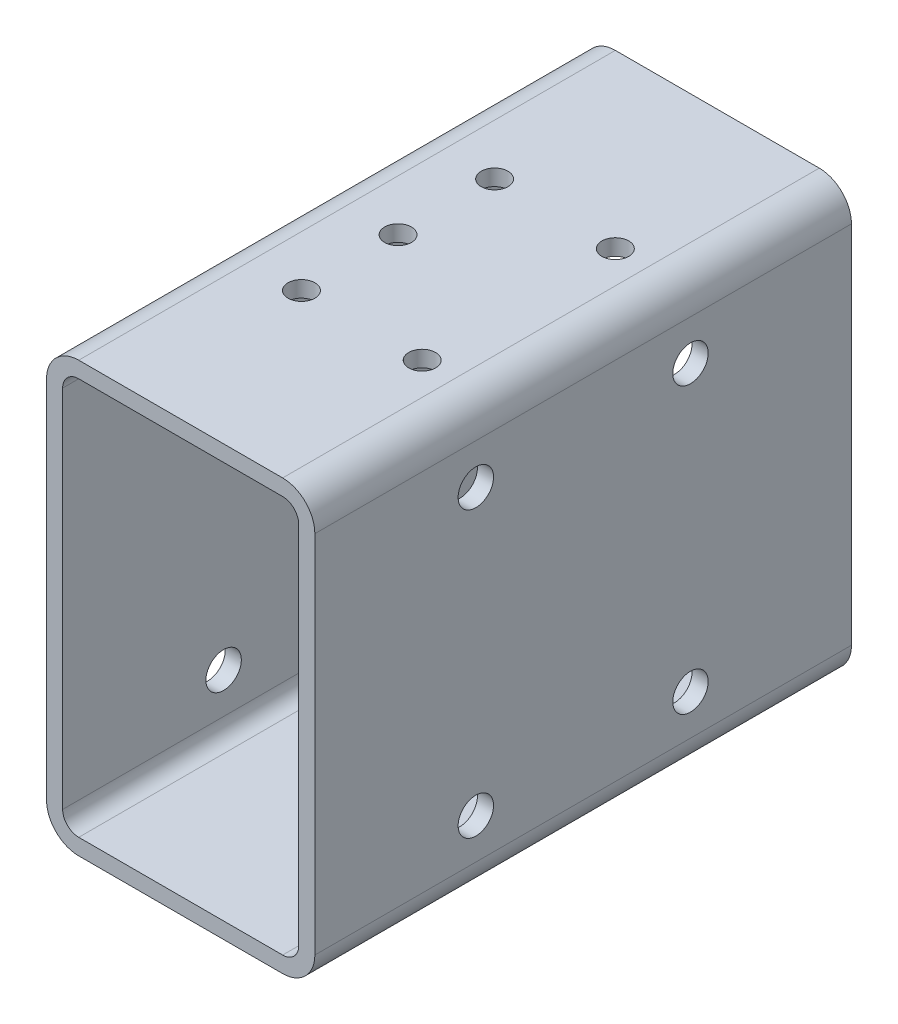
SolidWorks part; units mm, degrees
ref_plane "Front Plane" through (0, 0, 0) normal (0, 0, 1) x (1, 0, 0)
ref_plane "Top Plane" through (0, 0, 0) normal (0, 1, 0) x (1, 0, 0)
ref_plane "Right Plane" through (0, 0, 0) normal (1, 0, 0) x (0, 0, -1)
sketch "Sketch1" plane through (0, 0, 0) normal (0, 0, 1) x (1, 0, 0)
  line L0 (19, 37) -> (-19, 37)
  line L1 (19, -40) -> (-19, -40)
  line L2 (25, -34) -> (25, 34)
  line L3 (19, 40) -> (-19, 40)
  line L4 (-25, -34) -> (-25, 34)
  line L5 (25, -40) -> (-25, 40) construction
  line L6 (25, 40) -> (-25, -40) construction
  line L7 (-22, -34) -> (-22, 34)
  line L8 (19, -37) -> (-19, -37)
  line L9 (22, -34) -> (22, 34)
  arc A0 (-19, -40) -> (-25, -34) centre (-19, -34) cw
  arc A1 (19, -40) -> (25, -34) centre (19, -34) ccw
  arc A2 (25, 34) -> (19, 40) centre (19, 34) ccw
  arc A3 (-19, 40) -> (-25, 34) centre (-19, 34) ccw
  arc A4 (-19, 37) -> (-22, 34) centre (-19, 34) ccw
  arc A5 (-19, -37) -> (-22, -34) centre (-19, -34) cw
  arc A6 (19, -37) -> (22, -34) centre (19, -34) ccw
  arc A7 (22, 34) -> (19, 37) centre (19, 34) ccw
  point P0 (0, 0)
  dimension "D1" = 6
  dimension "D3" = 80
  dimension "D4" = 50
  dimension "D2" = 3
extrude "Boss-Extrude1" add sketch "Sketch1" along normal mid plane 100
sketch "Sketch2" plane through (25, 0, 0) normal (1, 0, 0) x (0, 0, -1)
  line L1 (20, 26.5) -> (-20, 26.5) construction
  line L2 (20, 26.5) -> (20, -26.5) construction
  line L3 (20, -26.5) -> (-20, -26.5) construction
  line L4 (-20, 26.5) -> (-20, -26.5) construction
  line L5 (20, 26.5) -> (-20, -26.5) construction
  line L6 (20, -26.5) -> (-20, 26.5) construction
  circle A0 centre (-20, 26.5) radius 3.3
  circle A1 centre (20, 26.5) radius 3.3
  circle A2 centre (20, -26.5) radius 3.3
  circle A3 centre (-20, -26.5) radius 3.3
  point P0 (0, 0)
  dimension "D3" = 6.6
  dimension "D1" = 53
  dimension "D2" = 40
extrude "Cut-Extrude1" cut sketch "Sketch2" against normal through all
sketch "Sketch3" plane through (0, 40, 0) normal (0, 1, 0) x (1, 0, 0)
  line L0 (-24.6642, 0) -> (5.453, 0) construction
  line L1 (-9.5, 18) -> (-9.5, -18) construction
  line L2 (-9.5, 18) -> (13, 18) construction
  line L3 (13, 18) -> (13, -18) construction
  line L4 (25, -50) -> (25, 50) construction
  circle A0 centre (-9.5, 18) radius 2.5
  circle A1 centre (-9.5, 0) radius 2.5
  circle A2 centre (-9.5, -18) radius 2.5
  circle A3 centre (13, 18) radius 2.5
  circle A4 centre (13, -18) radius 2.5
  point P5 (-9.5, 0)
  dimension "D2" = 5
  dimension "D1" = 36
  dimension "D3" = 22.5
  dimension "D4" = 12
extrude "Cut-Extrude2" cut sketch "Sketch3" against normal up to surface (3 mm away) up to face at (0, 37, 0)
equation "\"M5_tap\"=4.2mm       ' Below you can do mesurements as follows: cm, mm, ft, in, m, "
equation "\"M5_clearence\"=5.5mm"
equation "\"M6_tap\"=5mm"
equation "\"M6_clearence\"=6.6mm"
equation "\"work_area_width\"=1100mm"
equation "\"work_area_depth\"=900mm"
equation "\"D3@Sketch1\"=\"steel_zbox_width\""
equation "\"D4@Sketch1\"=\"steel_zbox_height\""
equation "\"D1@Sketch1\"=\"steel_zbox_radius\""
equation "\"D2@Sketch1\"=\"steel_zbox_wall_thickness\""
equation "\"D1@Boss-Extrude1\"=\"length\""
equation "\"steel_base_width\"=80mm"
equation "\"steel_base_height\"=50mm"
equation "\"steel_base_wall_thickness\"=3mm"
equation "\"steel_base_radius\"=6mm"
equation "\"steel_sides_width\"=80mm    'this tube is rotated so flip width/height"
equation "\"steel_sides_height\"=50mm    'this tube is rotated so flip width/height"
equation "\"steel_sides_wall_thickness\"=3mm"
equation "\"steel_sides_radius\"=6mm"
equation "\"steel_gantry_width\"=80mm    'this tube is rotated so flip width/height"
equation "\"steel_gantry_height\"=50mm    'this tube is rotated so flip width/height"
equation "\"steel_gantry_wall_thickness\"=3mm"
equation "\"steel_gantry_radius\"=6mm"
equation "\"D3@Sketch2\"=\"M6_clearence\""
equation "\"D2@Sketch3\"=\"M6_tap\""
equation "\"steel_rollers_width\"=80mm"
equation "\"steel_rollers_height\"=50mm    'keep as low as possible as this increases how big plastic parts are"
equation "\"steel_rollers_wall_thickness\"=3mm"
equation "\"steel_rollers_radius\"=6mm"
equation "\"steel_zbox_width\"=80mm     'if the gantry height (rotated) is too thick, a wider zbox is necessary"
equation "\"steel_zbox_height\"=50mm    'hole patteren changes as the zbox and gantry height (rotated) changes."
equation "\"steel_zbox_wall_thickness\"=3mm"
equation "\"steel_zbox_radius\"=6mm"
equation "\"D4@Sketch3\"=\"steel_zbox_radius\" * 2"
equation "\"length\"= 100mm"
